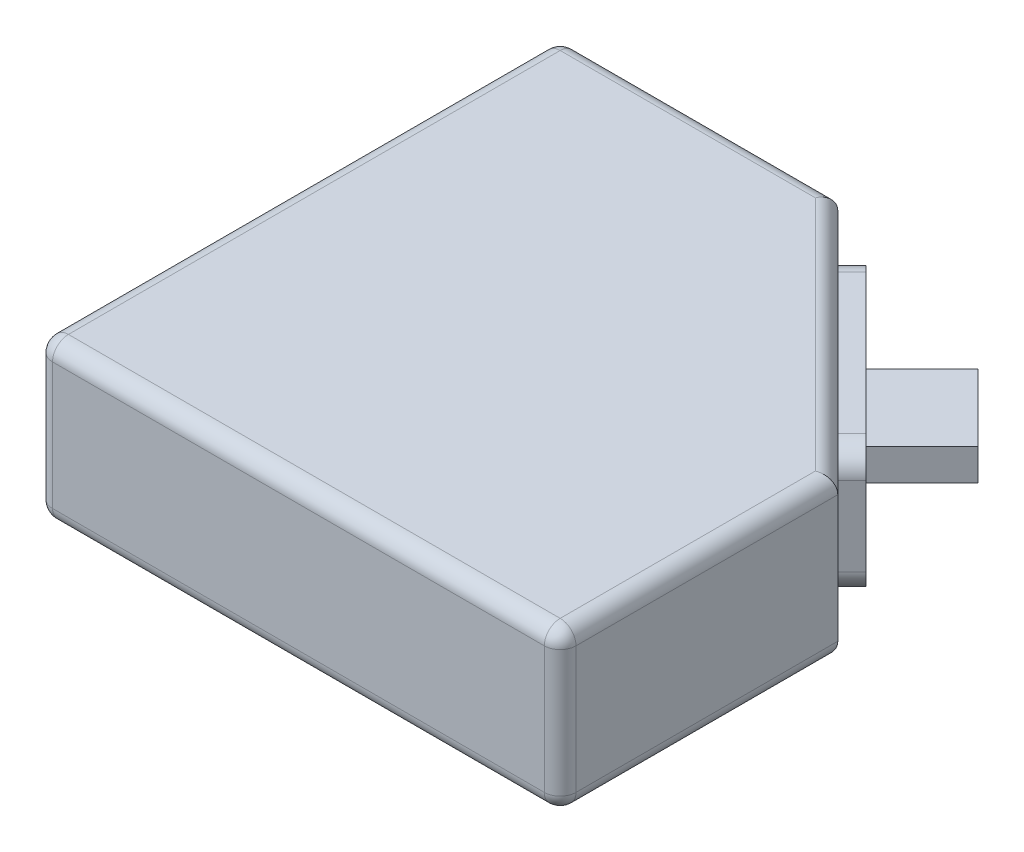
SolidWorks part; units mm, degrees
ref_plane "前视基准面" through (0, 0, 0) normal (0, 0, 1) x (1, 0, 0)
ref_plane "上视基准面" through (0, 0, 0) normal (0, 1, 0) x (1, 0, 0)
ref_plane "右视基准面" through (0, 0, 0) normal (1, 0, 0) x (0, 0, -1)
sketch "草图1" plane through (0, 0, 0) normal (0, 1, 0) x (1, 0, 0)
  line L0 (35, 66) -> (66, 35)
  line L1 (0, 0) -> (66, 0)
  line L2 (0, 0) -> (0, 66)
  line L3 (0, 66) -> (35, 66)
  line L4 (66, 0) -> (66, 35)
  dimension "D1" = 66
  dimension "D2" = 66
  dimension "D3" = 35
  dimension "D4" = 35
extrude "凸台-拉伸1" add sketch "草图1" along normal blind 20
sketch "草图2" plane through (50.5, 0, -50.5) normal (0.7071, 0, -0.7071) x (-0.7071, 0, -0.7071)
  line L0 (21.9203, 10) -> (-49.9183, 10) construction
  line L1 (21.9203, 20) -> (21.9203, 0) construction
  line L2 (0, 20) -> (0, -10.8202) construction
  line L3 (-21.9203, 20) -> (21.9203, 20) construction
  line L4 (15.5, 15) -> (15.5, 5)
  line L5 (12.5, 2) -> (-12.5, 2)
  line L6 (12.5, 18) -> (-12.5, 18)
  line L7 (-15.5, 15) -> (-15.5, 5)
  arc A0 (-15.5, 5) -> (-12.5, 2) centre (-12.5, 5) ccw
  arc A1 (-15.5, 15) -> (-12.5, 18) centre (-12.5, 15) cw
  arc A2 (15.5, 5) -> (12.5, 2) centre (12.5, 5) cw
  arc A3 (12.5, 18) -> (15.5, 15) centre (12.5, 15) cw
  point P14 (15.5, 10)
  point P15 (0, 2)
  point P16 (0, 18)
  point P18 (-15.5, 2)
  point P21 (-15.5, 18)
  point P24 (15.5, 2)
  point P27 (15.5, 18)
  dimension "D3" = 3
  dimension "D1" = 31
  dimension "D2" = 16
extrude "凸台-拉伸2" add sketch "草图2" along normal blind 2.5
sketch "草图3" plane through (52.2678, 0, -52.2678) normal (0.7071, 0, -0.7071) x (-0.7071, 0, -0.7071)
  line L0 (21.9203, 10) -> (-21.9203, 10) construction
  line L1 (21.9203, 20) -> (21.9203, 0) construction
  line L2 (-21.9203, 20) -> (-21.9203, 0) construction
  line L3 (0, 20) -> (0, 0) construction
  line L4 (-21.9203, 20) -> (21.9203, 20) construction
  line L5 (6, 12) -> (6, 8)
  line L6 (6, 8) -> (-6, 8)
  line L7 (6, 12) -> (-6, 12)
  line L8 (-6, 12) -> (-6, 8)
  point P16 (6, 10)
  point P17 (0, 8)
  point P18 (0, 12)
  dimension "D1" = 12
  dimension "D2" = 4
extrude "凸台-拉伸3" add sketch "草图3" along normal blind 10
fillet "圆角1" radius 2 13 edges at (33, 0, 0) (66, 0, -17.5) (50.5, 0, -50.5) (17.5, 0, -66) (0, 0, -33) (17.5, 20, -66) (50.5, 20, -50.5) (66, 20, -17.5) (33, 20, 0) (0, 20, -33) (66, 10, 0) (0, 10, -66) (0, 10, 0)
